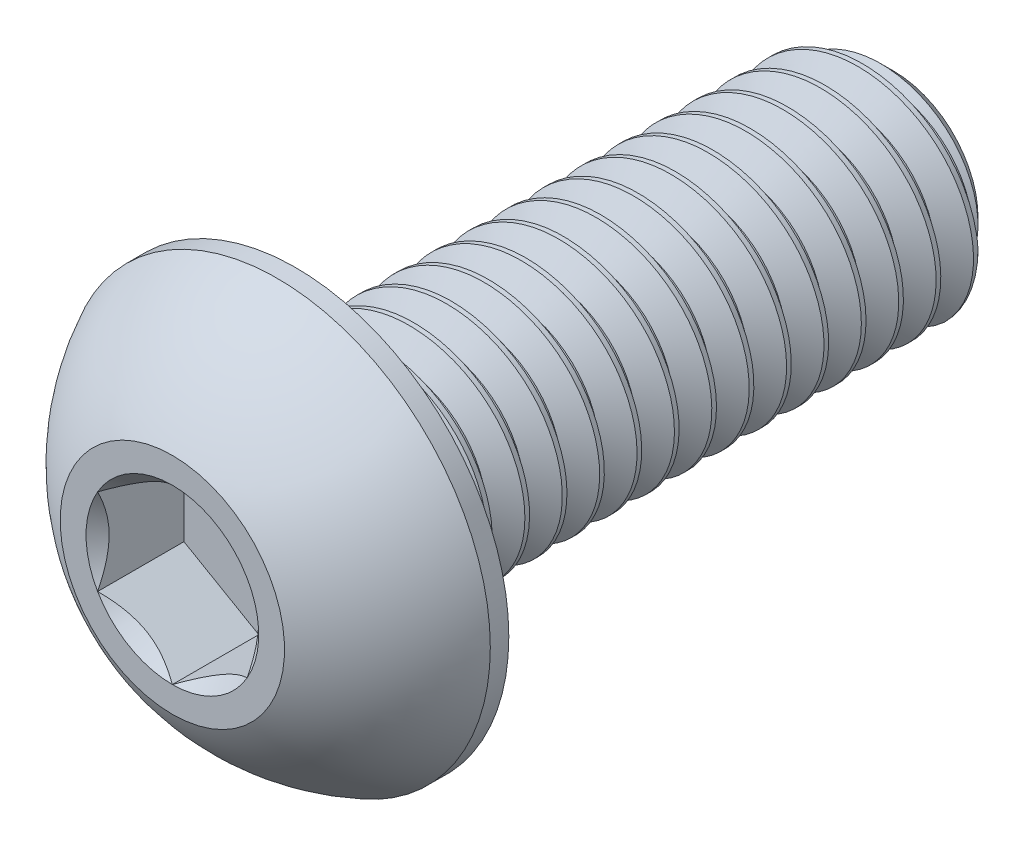
SolidWorks part; units mm, degrees
material "Alloy Steel"
ref_plane "Front" through (0, 0, 0) normal (0, 0, 1) x (1, 0, 0)
ref_plane "Top" through (0, 0, 0) normal (0, 1, 0) x (1, 0, 0)
ref_plane "Right" through (0, 0, 0) normal (1, 0, 0) x (0, 0, -1)
sketch "Sketch1" plane through (0, 0, 0) normal (1, 0, 0) x (0, 0, -1)
  line L2 (1.65, 1.5) -> (9.65, 1.5)
  line L3 (9.65, 1.5) -> (9.65, 0)
  line L4 (9.65, 0) -> (1.65, 0)
  line L6 (1.4025, 2.85) -> (1.65, 2.85) construction
  line L7 (9.65, 1.5) -> (9.65, -1.5) construction
  line L8 (0, 0) -> (1.65, 0) construction
  line L9 (1.65, 2.85) -> (1.65, -2.85) construction
  line L11 (1.65, 1.5) -> (1.65, 0)
  line L13 (0, 1) -> (0, -1) construction
  line L14 (0, 1) -> (0, 1.5) construction
  arc A3 (0, 1.5) -> (1.4025, 2.85) centre (2.7948, 0) cw construction
  dimension "D1" = 0.2475
  dimension "Head Ht" = 1.65
  dimension "Head Dia" = 5.7
  dimension "Dia" = 3
  dimension "Lg" = 8
  dimension "Hex" = 2
revolve "Revolve1" add sketch "Sketch1" angle 360 mid plane about L4
sketch "Sketch3" plane through (0, 0, -9.65) normal (0, 0, -1) x (-1, 0, 0)
  circle A0 centre (0, 0) radius 1.5
curve "Helix/Spiral1" pitch 0.5 height 8.5 radius 1.5 centre (0, 0, -9.65) axis (0, 0, 1) start towards (0, 1, 0)
sketch "Sketch2" plane through (0, 0, 0) normal (1, 0, 0) x (0, 0, -1)
  line L0 (9.65, 1.5) -> (10.0875, 1.5)
  line L1 (10.0875, 1.5) -> (9.9, 1.1752)
  line L2 (9.9, 1.1752) -> (9.8375, 1.1752)
  line L3 (9.8375, 1.1752) -> (9.65, 1.5)
  line L4 (9.7438, 1.3376) -> (9.9938, 1.3376) construction
  dimension "D1" = 60
  dimension "D2" = 0.0625
  dimension "D3" = 0.25
chamfer "Chamfer1" distance 0.375 angle 45 1 edges at (0, 1.5, -9.65)
sweep "Cut-Sweep1" cut profiles "Sketch2" path "Helix/Spiral1" align with end faces yes
sketch "Sketch7" plane through (0, 0, 0) normal (1, 0, 0) x (0, 0, -1)
  line L6 (1.4025, 2.85) -> (1.65, 2.85) construction
  line L8 (0, 0) -> (1.65, 0) construction
  line L11 (1.65, 2.85) -> (1.65, -2.85) construction
  line L12 (1.4025, 2.85) -> (1.65, 2.85)
  line L13 (0, 0) -> (1.65, 0)
  line L14 (0, 1) -> (0, -1) construction
  line L15 (1.65, 2.85) -> (1.65, 0)
  line L16 (0, 1.5) -> (0, 0)
  arc A2 (1.4025, 2.85) -> (0, 1.5) centre (2.7948, 0) ccw construction
  arc A3 (1.4025, 2.85) -> (0, 1.5) centre (2.7948, 0) ccw
revolve "Revolve2" add sketch "Sketch7" angle 360 mid plane about L13
sketch "Sketch5" plane through (0, 0, 0) normal (0, 0, 1) x (1, 0, 0)
  line L1 (1, -0.5774) -> (1, 0.5774)
  line L2 (1, 0.5774) -> (0, 1.1547)
  line L3 (0, 1.1547) -> (-1, 0.5774)
  line L4 (-1, 0.5774) -> (-1, -0.5774)
  line L5 (-1, -0.5774) -> (0, -1.1547)
  line L6 (0, -1.1547) -> (1, -0.5774)
  circle A0 centre (0, 0) radius 1 construction
extrude "Cut-Extrude2" cut sketch "Sketch5" against normal blind 1.155
sketch "Sketch6" plane through (0, 0, 0) normal (0, 0, 1) x (1, 0, 0)
  circle A0 centre (0, 0) radius 1.1547
extrude "Cut-Extrude3" cut sketch "Sketch6" against normal blind 1.155 draft 45
sketch "Sketch9" [suppressed] plane through (0, 0, -5.0546) normal (0, 0, 1) x (1, 0, 0)
  circle A2 centre (0, 0) radius 4.7625
extrude "Boss-Extrude2" [suppressed] add sketch "Sketch9" against normal offset from surface (6.35 mm away) 31.75 up to face at (0, 1.125, -9.65)
sketch "Sketch10" plane through (0, 0, 0) normal (1, 0, 0) x (0, 0, -1)
  line L0 (9.65, 1.5) -> (9.65, -1.5) construction
  point P0 (8.9, -1.5)
  dimension "D1" = 0.75
equation "\"D3@Helix/Spiral1\" = \"Lg@Sketch1\" + \"D4@Helix/Spiral1\""
equation "\"D2@Sketch2\" = \"D4@Helix/Spiral1\" * .125"
equation "\"D3@Sketch2\" = \"D4@Helix/Spiral1\" * .5"
equation "\"D1@Chamfer1\" = \"D4@Helix/Spiral1\" * .75"
equation "\"D1@Cut-Extrude2\" = \"Head Ht@Sketch1\" * .7"
equation "\"D1@Sketch1\" = \"Head Ht@Sketch1\" * .15"
equation "\"D1@Sketch10\" = \"D4@Helix/Spiral1\" * 1.5"
equation "\"D1@Cut-Extrude3\" = \"D1@Cut-Extrude2\""
